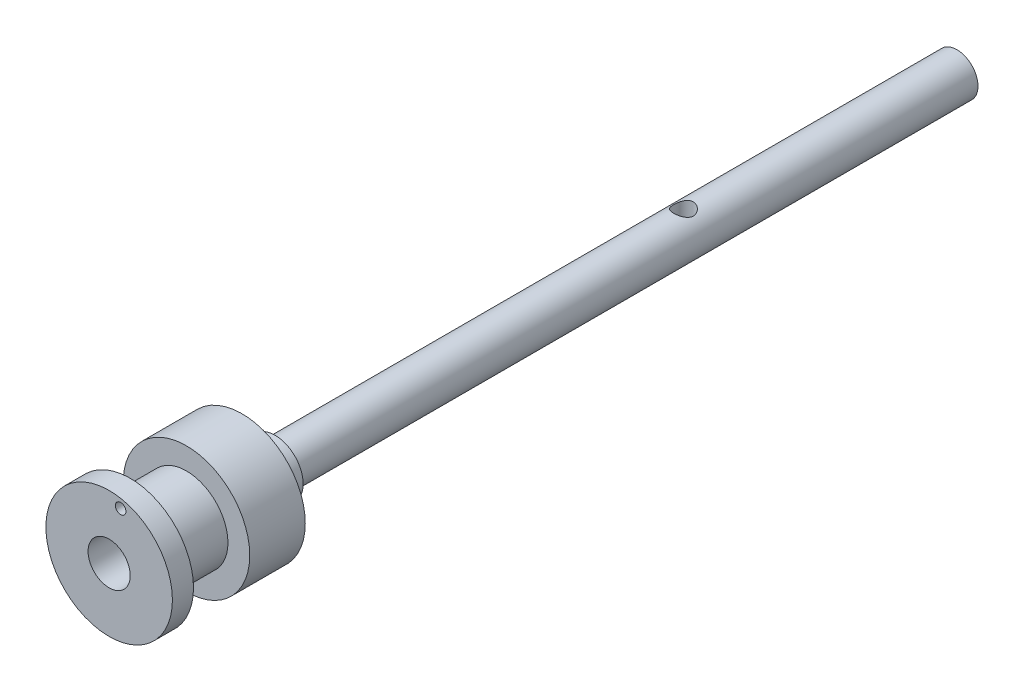
SolidWorks part; units mm, degrees
material "1060 Alloy"
ref_plane "Front Plane" through (0, 0, 0) normal (0, 0, 1) x (1, 0, 0)
ref_plane "Top Plane" through (0, 0, 0) normal (0, 1, 0) x (1, 0, 0)
ref_plane "Right Plane" through (0, 0, 0) normal (1, 0, 0) x (0, 0, -1)
sketch "Sketch1" plane through (0, 0, 0) normal (0, 0, 1) x (1, 0, 0)
  circle A0 centre (0, 0) radius 3
  dimension "D1" = 6
extrude "Boss-Extrude1" add sketch "Sketch1" along normal blind 97
sketch "Sketch2" plane through (0, 0, 97) normal (0, 0, 1) x (1, 0, 0)
  circle A0 centre (0, 0) radius 4
  dimension "D1" = 8
extrude "Boss-Extrude2" add sketch "Sketch2" along normal blind 4.7
sketch "Sketch3" plane through (0, 0, 101.7) normal (0, 0, 1) x (1, 0, 0)
  circle A0 centre (0, 0) radius 9
  dimension "D1" = 18
extrude "Boss-Extrude3" add sketch "Sketch3" along normal blind 7.9
sketch "Sketch4" plane through (0, 0, 109.6) normal (0, 0, 1) x (1, 0, 0)
  circle A0 centre (0, 0) radius 5.9
  dimension "D1" = 11.8
extrude "Boss-Extrude4" add sketch "Sketch4" along normal blind 8
sketch "Sketch5" plane through (0, 0, 117.6) normal (0, 0, 1) x (1, 0, 0)
  circle A0 centre (0, 0) radius 9
  dimension "D1" = 18
extrude "Boss-Extrude5" add sketch "Sketch5" along normal blind 3
sketch "Sketch6" plane through (0, 0, 0) normal (0, 1, 0) x (1, 0, 0)
  line L0 (0, 0) -> (0, -38.9) construction
  circle A0 centre (0, -38.9) radius 1.4
  dimension "D2" = 2.8
  dimension "D1" = 38.9
extrude "Cut-Extrude1" cut sketch "Sketch6" against normal blind 82 and the other way blind 82
sketch "Sketch7" plane through (0, 0, 120.6) normal (0, 0, 1) x (1, 0, 0)
  circle A0 centre (0, 0) radius 3
  circle A1 centre (1.6378, 7.5882) radius 0.75
  dimension "D1" = 6
  dimension "D2" = 1.5
extrude "Cut-Extrude2" cut sketch "Sketch7" against normal blind 9
